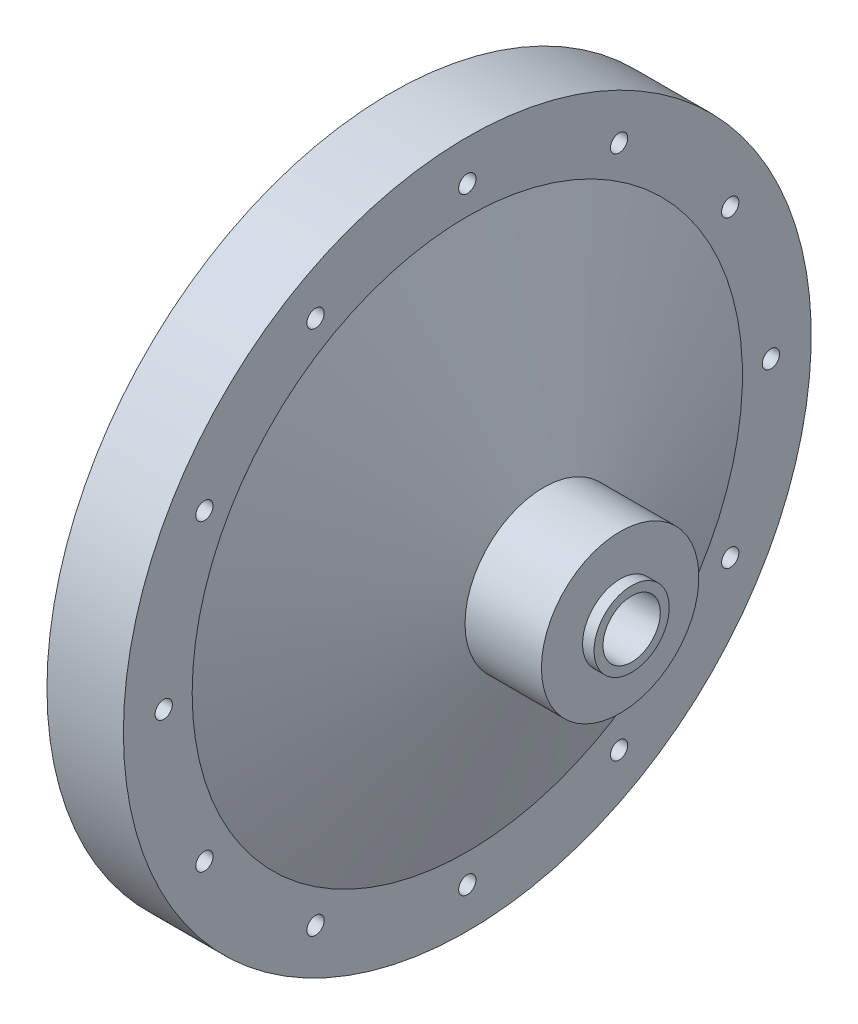
SolidWorks part; units mm, degrees
material "6061-T6 (SS)"
ref_plane "Front Plane" through (0, 0, 0) normal (0, 0, 1) x (1, 0, 0)
ref_plane "Top Plane" through (0, 0, 0) normal (0, 1, 0) x (1, 0, 0)
ref_plane "Right Plane" through (0, 0, 0) normal (1, 0, 0) x (0, 0, -1)
sketch "Sketch2" plane through (0, 0, 0) normal (0, 0, 1) x (1, 0, 0)
  line L0 (0, 0) -> (165.0115, 0) construction
  line L1 (0, 0) -> (0, 57.15)
  line L2 (0, 57.15) -> (12.7, 57.15)
  line L3 (12.7, 57.15) -> (12.7, 45.72)
  line L4 (12.7, 45.72) -> (25.4, 13.081)
  line L5 (38.1, 13.081) -> (38.1, 6.2484)
  line L6 (25.4, 13.081) -> (38.1, 13.081)
  line L7 (38.1, 6.2484) -> (40.005, 6.2484)
  line L8 (40.005, 6.2484) -> (40.005, 0)
  line L9 (0, 0) -> (40.005, 0)
  dimension "D1" = 57.15
  dimension "D2" = 12.7
  dimension "D3" = 45.72
  dimension "D4" = 13.081
  dimension "D5" = 12.7
  dimension "D6" = 12.7
  dimension "D7" = 6.2484
  dimension "D8" = 1.905
revolve "Revolve1" add sketch "Sketch2" angle 360 about L0
cosmetic thread "Cosmetic Thread1" parameters "D2"=23.1953
sketch "Sketch3" plane through (40.005, 0, 0) normal (1, 0, 0) x (0, 0, -1)
  circle A0 centre (0, 0) radius 4.7625
  dimension "D1" = 9.525
extrude "Cut-Extrude1" cut sketch "Sketch3" against normal through all
sketch "Sketch4" plane through (0, 0, 0) normal (-1, 0, 0) x (0, 0, 1)
  circle A0 centre (0, 0) radius 50.4444 construction
  circle A1 centre (0, -50.4444) radius 2.146
  circle A2 centre (-25.2222, -43.6861) radius 2.146
  circle A3 centre (-43.6861, -25.2222) radius 2.146
  circle A4 centre (-50.4444, 0) radius 2.146
  circle A5 centre (-43.6861, 25.2222) radius 2.146
  circle A6 centre (-25.2222, 43.6861) radius 2.146
  circle A7 centre (0, 50.4444) radius 2.146
  circle A8 centre (25.2222, 43.6861) radius 2.146
  circle A9 centre (43.6861, 25.2222) radius 2.146
  circle A10 centre (50.4444, 0) radius 2.146
  circle A11 centre (43.6861, -25.2222) radius 2.146
  circle A12 centre (25.2222, -43.6861) radius 2.146
  point P29 (0, 0)
  dimension "D1" = 12
hole_wizard "#33 (0.113) Diameter Hole1" positions "Sketch7" profile "Sketch8" hole size "#33" standard "ANSI Inch"
sketch "Sketch7" plane through (0, 0, 0) normal (-1, 0, 0) x (0, 0, 1)
  point P0 (0, -50.4444)
  point P3 (-25.2222, -43.6861)
  point P6 (-43.6861, -25.2222)
  point P9 (-50.4444, 0)
  point P12 (-43.6861, 25.2222)
  point P15 (-25.2222, 43.6861)
  point P18 (0, 50.4444)
  point P21 (25.2222, 43.6861)
  point P24 (43.6861, 25.2222)
  point P27 (50.4444, 0)
  point P30 (43.6861, -25.2222)
  point P33 (25.2222, -43.6861)
sketch "Sketch8" plane through (0, -50.4444, 0) normal (0, 1, 0) x (0, 0, 1)
  line L0 (0, 0) -> (0, 26.2623)
  line L1 (0, 26.2623) -> (1.4351, 25.4)
  line L2 (1.4351, 25.4) -> (1.4351, 0)
  line L5 (1.4351, 0) -> (0, 0)
  line L10 (0, 26.2623) -> (-1.4351, 25.4) construction
  line L11 (0, -6.35) -> (0, 107.95) construction
  dimension "Hole Dia." = 2.8702
  dimension "Hole Depth" = 25.4
  dimension "Drill Angle" = 118
sketch "Sketch9" plane through (0, 0, 0) normal (-1, 0, 0) x (0, 0, 1)
  line L0 (0, 0) -> (-67.6727, 18.1329) construction
  line L1 (0, 0) -> (-50.4444, 0) construction
  circle A0 centre (0, 0) radius 50.4444 construction
  circle A1 centre (-48.7255, 13.056) radius 2.9451
  circle A2 centre (48.7255, -13.056) radius 2.9451
  point P14 (0, 0)
  dimension "D1" = 15
  dimension "D2" = 2
hole_wizard "3/16 (0.1875) Dowel Hole1" positions "Sketch10" profile "Sketch11" hole size "3/16" standard "ANSI Inch"
sketch "Sketch10" plane through (0, 0, 0) normal (-1, 0, 0) x (0, 0, 1)
  point P0 (48.7255, -13.056)
  point P3 (-48.7255, 13.056)
sketch "Sketch11" plane through (0, -13.056, 48.7255) normal (0, 1, 0) x (0, 0, 1)
  line L0 (0, 0) -> (0, 7.7808)
  line L1 (0, 7.7808) -> (2.3812, 6.35)
  line L2 (2.3812, 6.35) -> (2.3812, 0)
  line L5 (2.3812, 0) -> (0, 0)
  line L10 (0, 7.7808) -> (-2.3812, 6.35) construction
  line L11 (0, -6.35) -> (0, 107.95) construction
  dimension "Hole Dia." = 4.7625
  dimension "Hole Depth" = 6.35
  dimension "Drill Angle" = 118
sketch "Sketch12" plane through (0, 0, 0) normal (-1, 0, 0) x (0, 0, 1)
  circle A0 centre (0, 0) radius 38.1
  dimension "D1" = 76.2
extrude "Cut-Extrude2" cut sketch "Sketch12" against normal blind 3.81
ref_plane "Plane1" through (6.35, 0, 0) normal (-1, 0, 0) x (0, 0, 1)
sketch "Sketch14" plane through (3.81, 0, 0) normal (-1, 0, 0) x (0, 0, 1)
  circle A0 centre (0, 0) radius 38.1
  dimension "D1" = 76.2
sketch "Sketch15" plane through (6.35, 0, 0) normal (-1, 0, 0) x (0, 0, 1)
  circle A0 centre (0, 0) radius 38.0873
  dimension "D1" = 76.1746
loft "Cut-Loft2" cut profiles "Sketch14", "Sketch15" connector at (3.81, 0, 38.1) connector at (6.35, 0, 38.0873)
sketch "Sketch16" plane through (6.35, 0, 0) normal (-1, 0, 0) x (0, 0, 1)
  circle A0 centre (0, 0) radius 28.575
  dimension "D1" = 57.15
ref_plane "Plane2" through (21.59, 0, 0) normal (-1, 0, 0) x (0, 0, 1)
sketch "Sketch17" plane through (21.59, 0, 0) normal (-1, 0, 0) x (0, 0, 1)
  circle A0 centre (0, 0) radius 4.7625
  dimension "D1" = 9.525
loft "Cut-Loft3" cut profiles "Sketch16", "Sketch17" connector at (6.35, 0, 28.575) connector at (21.59, 0, 4.7625)
fillet "Fillet1" radius 3.175 1 edges at (21.59, 0, 4.7625)
sketch "Sketch18" plane through (6.35, 0, 0) normal (-1, 0, 0) x (0, 0, 1)
  circle A0 centre (0, 0) radius 33.3375
  circle A1 centre (33.3375, 0) radius 1.5042
  dimension "D1" = 66.675
hole_wizard "Tap Drill for #4-40 Tap1" positions "Sketch19" profile "Sketch20" hole size "#4-40" standard "ANSI Inch"
sketch "Sketch19" plane through (6.35, 0, 0) normal (-1, 0, 0) x (0, 0, 1)
  point P0 (33.3375, 0)
sketch "Sketch20" plane through (6.35, 0, 33.3375) normal (0, 1, 0) x (0, 0, 1)
  line L0 (0, 0) -> (0, 7.0292)
  line L1 (0, 7.0292) -> (1.1303, 6.35)
  line L2 (1.1303, 6.35) -> (1.1303, 0)
  line L5 (1.1303, 0) -> (0, 0)
  line L10 (0, 7.0292) -> (-1.1303, 6.35) construction
  line L11 (0, -6.35) -> (0, 107.95) construction
  dimension "Hole Dia." = 2.2606
  dimension "Hole Depth" = 6.35
  dimension "Drill Angle" = 118
pattern_circular "CirPattern1" count 8 over 360 about axis through (3.81, 0, 0) along (-1, 0, 0) of "Tap Drill for #4-40 Tap1"
chamfer "Chamfer1" distance 0.127 angle 45 1 edges at (6.35, 0, 38.0873) first distance on face at (3.81, 0, 38.1)
